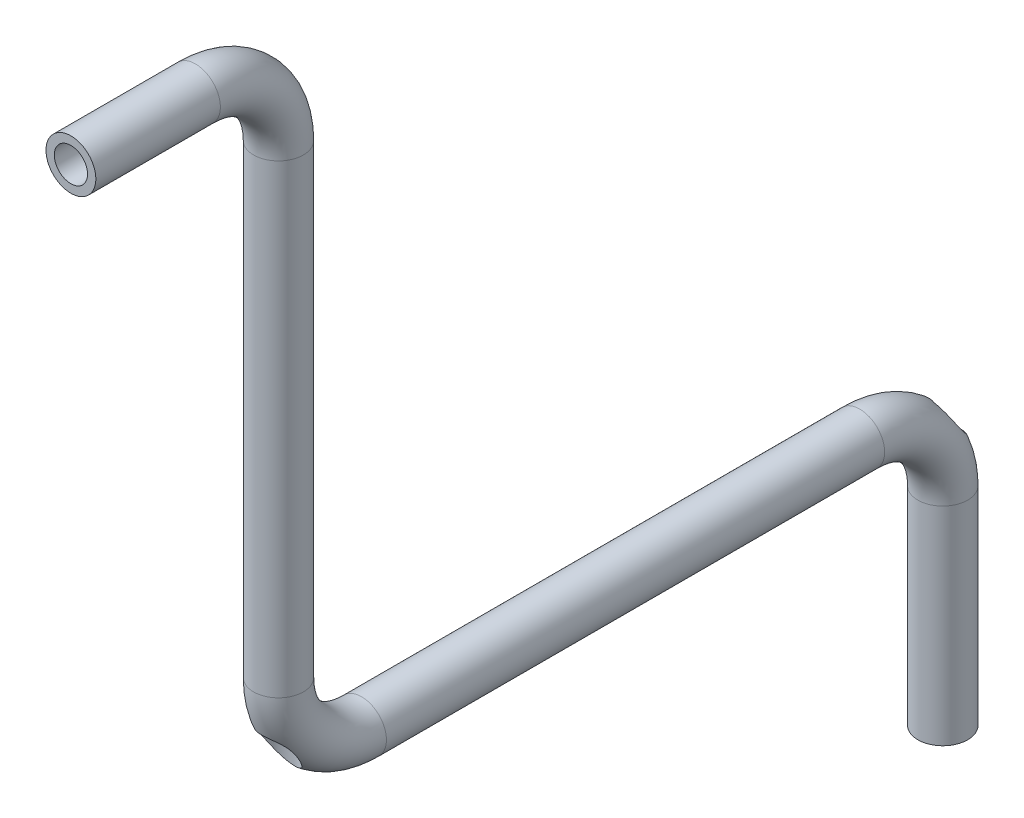
SolidWorks part; units mm, degrees
ref_plane "Front Plane" through (0, 0, 0) normal (0, 0, 1) x (1, 0, 0)
ref_plane "Top Plane" through (0, 0, 0) normal (0, 1, 0) x (1, 0, 0)
ref_plane "Right Plane" through (0, 0, 0) normal (1, 0, 0) x (0, 0, -1)
sketch "Sketch1" plane through (0, 0, 0) normal (1, 0, 0) x (0, 0, -1)
  line L0 (0, 660) -> (0, 100)
  line L1 (100, 0) -> (700, 0)
  line L2 (800, -100) -> (800, -350)
  line L3 (-100, 760) -> (-250, 760)
  arc A0 (0, 100) -> (100, 0) centre (100, 100) ccw
  arc A1 (0, 660) -> (-100, 760) centre (-100, 660) ccw
  arc A2 (700, 0) -> (800, -100) centre (700, -100) cw
  point P7 (0, 0)
  point P13 (800, 0)
  dimension "D4" = 100
  dimension "D1" = 100
  dimension "D5" = 100
  dimension "D2" = 800
  dimension "D3" = 350
sweep "Sweep-Thin2" add path "Sketch1" circular profile diameter 60 parameters "D1"=10, "D3"=60
sketch "Sketch25" plane through (0, 0, 0) normal (0, 1, 0) x (1, 0, 0)
  circle A0 centre (0, 0) radius 20
extrude "Cut-Extrude1" cut sketch "Sketch25" against normal blind 10 and the other way blind 86
ref_plane "Plane1" through (0, 0, -330) normal (0, 0, 1) x (1, 0, 0)
sketch "Sketch28" plane through (0, 0, -330) normal (0, 0, 1) x (1, 0, 0)
  circle A0 centre (0, 370) radius 20
  dimension "D1" = 370
extrude "Cut-Extrude2" cut sketch "Sketch28" against normal blind 10 and the other way blind 312
sketch "Sketch29" plane through (0, 0, 0) normal (0, 1, 0) x (1, 0, 0)
  circle A1 centre (0, 800) radius 20.009
  point P2 (0, 0)
extrude "Cut-Extrude4" cut sketch "Sketch29" against normal blind 64
